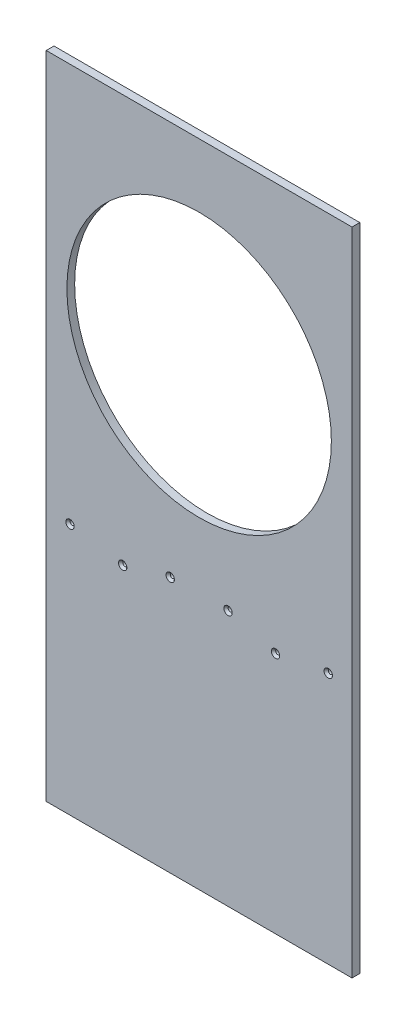
SolidWorks part; units mm, degrees
material "Pine"
ref_plane "Front Plane" through (0, 0, 0) normal (0, 0, 1) x (1, 0, 0)
ref_plane "Top Plane" through (0, 0, 0) normal (0, 1, 0) x (1, 0, 0)
ref_plane "Right Plane" through (0, 0, 0) normal (1, 0, 0) x (0, 0, -1)
sketch "Sketch1" plane through (0, 0, 0) normal (0, 0, 1) x (1, 0, 0)
  line L0 (-182.4801, 0) -> (287.4199, 0)
  line L2 (-182.4801, 0) -> (-182.4801, -999.49)
  line L3 (-182.4801, -999.49) -> (287.4199, -999.49)
  line L4 (287.4199, 0) -> (287.4199, -999.49)
  circle A0 centre (52.4699, -300.99) radius 203.2
  point P8 (52.4699, -97.79)
  dimension "D3" = 406.4
  dimension "D4" = 234.95
  dimension "D5" = 698.5
  dimension "D1" = 469.9
  dimension "D2" = 999.49
  dimension "D6" = 97.79
  dimension "D7" = 300.99
extrude "Boss-Extrude1" add sketch "Sketch1" along normal blind 11.9062
hole_wizard "CSK for 1/4 Flat Head Machine Screw1" positions "Sketch2" profile "Sketch3" countersink size "1/4" standard "ANSI Inch" end condition through all
sketch "Sketch2" plane through (0, 0, 11.9062) normal (0, 0, 1) x (1, 0, 0)
  line L1 (-182.4801, -999.49) -> (287.4199, -999.49) construction
  line L2 (287.4199, -999.49) -> (287.4199, 0) construction
  point P0 (-145.9676, -612.14)
  point P2 (-65.0051, -626.4275)
  point P4 (8.0199, -605.79)
  point P6 (96.9199, -605.79)
  point P8 (169.9449, -626.4275)
  point P10 (250.9074, -612.14)
  dimension "D1" = 387.35
  dimension "D2" = 373.0625
  dimension "D3" = 393.7
  dimension "D4" = 36.5125
  dimension "D5" = 117.475
  dimension "D6" = 190.5
  dimension "D7" = 279.4
  dimension "D8" = 352.425
  dimension "D9" = 433.3875
sketch "Sketch3" plane through (-145.9676, -612.14, 11.9062) normal (1, 0, 0) x (0, -1, 0)
  line L0 (0, 0) -> (0, 11.9062)
  line L1 (0, 11.9062) -> (3.3782, 11.9062)
  line L2 (3.3782, 11.9062) -> (3.3782, 3.5209)
  line L3 (3.3782, 3.5209) -> (6.4389, 0)
  line L5 (6.4389, 0) -> (0, 0)
  line L6 (-3.3782, 3.5209) -> (-6.4389, 0) construction
  line L11 (0, -6.35) -> (0, 107.95) construction
  dimension "Thru Hole Dia." = 6.7564
  dimension "Thru Hole Depth" = 11.9062
  dimension "Near C'Sink Dia." = 12.8778
  dimension "Near C'Sink Angle" = 82
